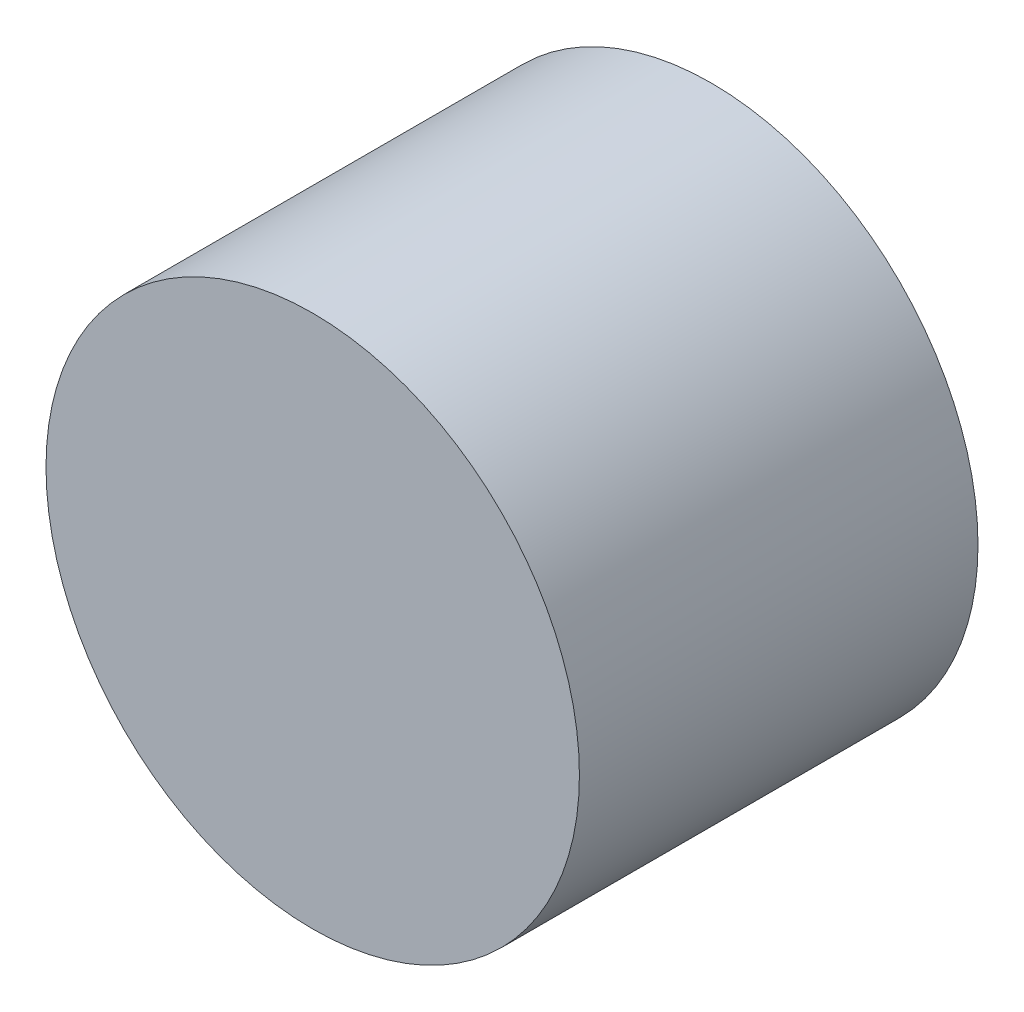
SolidWorks part; units mm, degrees
ref_plane "Front Plane" through (0, 0, 0) normal (0, 0, 1) x (1, 0, 0)
ref_plane "Top Plane" through (0, 0, 0) normal (0, 1, 0) x (1, 0, 0)
ref_plane "Right Plane" through (0, 0, 0) normal (1, 0, 0) x (0, 0, -1)
sketch "Sketch1" plane through (0, 0, 0) normal (0, 0, 1) x (1, 0, 0)
  circle A1 centre (0, 0) radius 4.015
  dimension "D1" = 8.03
extrude "Boss-Extrude1" add sketch "Sketch1" along normal blind 6
equation "\"Outer\"= 8.03"
equation "\"Depth\"= 6"
equation "\"D1@Sketch1\"=\"Outer\""
equation "\"D1@Boss-Extrude1\"=\"Depth\""
